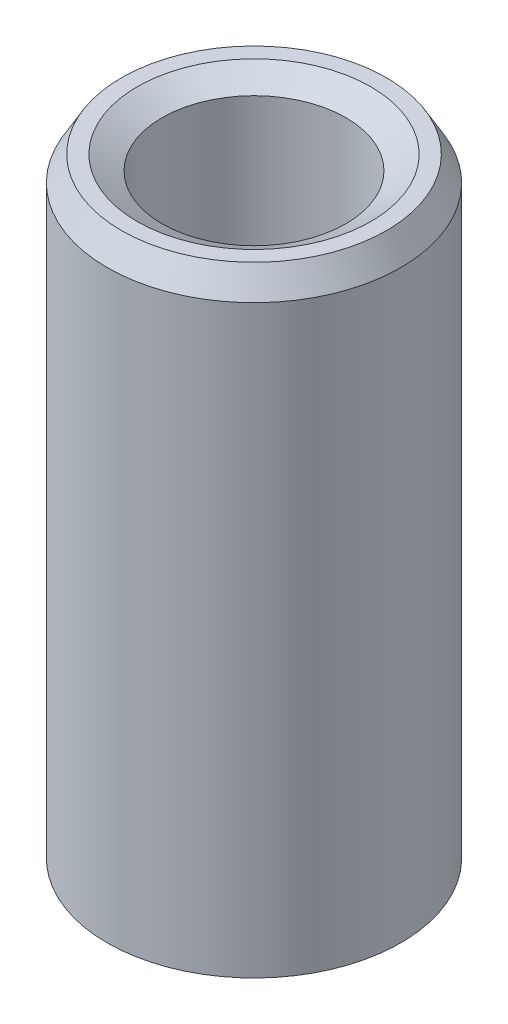
SolidWorks part; units mm, degrees
ref_plane "Front Plane" through (0, 0, 0) normal (0, 0, 1) x (1, 0, 0)
ref_plane "Top Plane" through (0, 0, 0) normal (0, 1, 0) x (1, 0, 0)
ref_plane "Right Plane" through (0, 0, 0) normal (1, 0, 0) x (0, 0, -1)
sketch "Sketch1" plane through (0, 0, 0) normal (0, 1, 0) x (1, 0, 0)
  circle A0 centre (0, 0) radius 17.5
  dimension "SLEEVE_OD" = 35
extrude "Boss-Extrude1" add sketch "Sketch1" along normal blind 74.3816
sketch "Sketch2" plane through (0, 0, 0) normal (0, 1, 0) x (1, 0, 0)
  circle A0 centre (0, 0) radius 10.9579
  dimension "BORE_D" = 21.9158
extrude "Cut-Extrude1" cut sketch "Sketch2" along normal through all
chamfer "Chamfer1" distance 2.9625 angle 30 4 edges at (0, 74.3816, 10.9579) (0, 0, 10.9579) (0, 0, 17.5) (0, 74.3816, 17.5) first distance on face at (0, 74.3816, 10.9579) first distance on face at (0, 0, 10.9579) first distance on face at (0, 74.3816, 17.5)
